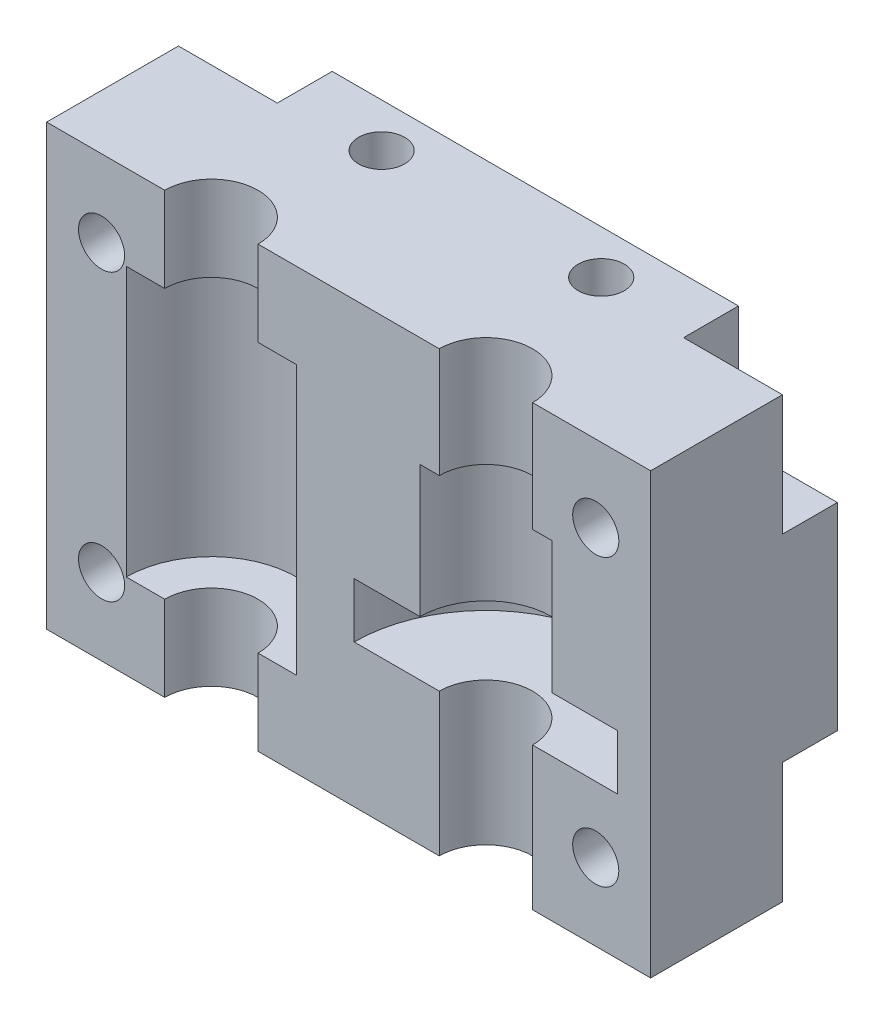
SolidWorks part; units mm, degrees
ref_plane "Plan de face" through (0, 0, 0) normal (0, 0, 1) x (1, 0, 0)
ref_plane "Plan de dessus" through (0, 0, 0) normal (0, 1, 0) x (1, 0, 0)
ref_plane "Plan de droite" through (0, 0, 0) normal (1, 0, 0) x (0, 0, -1)
sketch "Esquisse1" plane through (0, 0, 0) normal (0, 0, 1) x (1, 0, 0)
  line L1 (-27.5, -22.5) -> (27.5, -22.5)
  line L2 (-27.5, -22.5) -> (-27.5, 22.5)
  line L3 (-27.5, 22.5) -> (27.5, 22.5)
  line L4 (27.5, -22.5) -> (27.5, 22.5)
  line L5 (-27.5, -22.5) -> (27.5, 22.5) construction
  line L6 (-27.5, 22.5) -> (27.5, -22.5) construction
  point P0 (0, 0)
  dimension "D1" = 55
  dimension "D2" = 45
extrude "Boss.-Extru.1" add sketch "Esquisse1" along normal blind 12
sketch "Esquisse2" plane through (0, 22.5, 0) normal (0, 1, 0) x (1, 0, 0)
  line L0 (27.5, -12) -> (-27.5, -12) construction
  line L1 (-27.5, -12) -> (-27.5, 0) construction
  line L2 (27.5, -12) -> (27.5, 0) construction
  circle A0 centre (-12.5, -12) radius 4.25
  circle A1 centre (12.5, -12) radius 4.25
  dimension "D1" = 8.5
  dimension "D3" = 8.5
  dimension "D2" = 15
  dimension "D4" = 15
extrude "Enlèv. mat.-Extru.1" cut sketch "Esquisse2" against normal through all
sketch "Esquisse3" plane through (0, 0, 0) normal (0, 1, 0) x (1, 0, 0)
  circle A0 centre (-12.5, -12) radius 7.75
  dimension "D1" = 15.5
extrude "Enlèv. mat.-Extru.2" cut sketch "Esquisse3" against normal blind 12.25 and the other way blind 12.25
sketch "Esquisse9" plane through (0, 0, 12) normal (0, 0, 1) x (1, 0, 0)
  line L0 (-8.25, -22.5) -> (8.25, -22.5) construction
  line L1 (-30.9208, -30.2281) -> (30.1419, -30.2281)
  line L2 (-30.9208, -30.2281) -> (-30.9208, -18)
  line L3 (-30.9208, -18) -> (30.1419, -18)
  line L4 (30.1419, -30.2281) -> (30.1419, -18)
  line L5 (8.25, 22.5) -> (-8.25, 22.5) construction
  line L6 (31.3881, 26.1002) -> (-28.039, 26.1002)
  line L7 (31.3881, 26.1002) -> (31.3881, 18)
  line L8 (31.3881, 18) -> (-28.039, 18)
  line L9 (-28.039, 26.1002) -> (-28.039, 18)
  dimension "D1" = 4.5
  dimension "D2" = 4.5
extrude "Enlèv. mat.-Extru.7" cut sketch "Esquisse9" against normal blind 31
sketch "Sketch1" plane through (0, 0, 0) normal (0, 0, -1) x (-1, 0, 0)
  line L4 (-27.5, -18) -> (27.5, -18)
  line L5 (27.5, -18) -> (27.5, 18)
  line L6 (27.5, 18) -> (-27.5, 18)
  line L7 (-27.5, 18) -> (-27.5, -18)
  line L8 (-27.5, -18) -> (27.5, -18)
  line L9 (27.5, -18) -> (27.5, 18)
  line L10 (27.5, 18) -> (-27.5, 18)
  line L11 (-27.5, 18) -> (-27.5, -18)
  dimension "D1" = 0
extrude "Boss-Extrude1" add sketch "Sketch1" along normal blind 5
sketch "Sketch2" plane through (0, 0, 12) normal (0, 0, 1) x (1, 0, 0)
  line L0 (-27.5, 18) -> (-16.75, 18) construction
  line L1 (-27.5, 18) -> (-27.5, -18) construction
  line L2 (0, 18) -> (0, -18) construction
  line L3 (-8.25, 18) -> (8.25, 18) construction
  line L4 (8.25, -18) -> (-8.25, -18) construction
  line L5 (-27.5, 0) -> (27.5, 0) construction
  line L6 (27.5, -18) -> (27.5, 18) construction
  circle A0 centre (-22.5, 13) radius 2.1
  circle A1 centre (22.5, 13) radius 2.1
  circle A2 centre (22.5, -13) radius 2.1
  circle A3 centre (-22.5, -13) radius 2.1
  dimension "D1" = 4.2
  dimension "D2" = 5
  dimension "D3" = 5
extrude "Cut-Extrude1" cut sketch "Sketch2" against normal through all
sketch "Sketch3" plane through (0, 0, -5) normal (0, 0, -1) x (-1, 0, 0)
  circle A0 centre (-22.5, 13) radius 4
  circle A1 centre (22.5, 13) radius 4
  circle A2 centre (22.5, -13) radius 4
  circle A3 centre (-22.5, -13) radius 4
  dimension "D1" = 8
extrude "Cut-Extrude2" cut sketch "Sketch3" against normal blind 10
sketch "Sketch4" plane through (0, 0, -5) normal (0, 0, -1) x (-1, 0, 0)
  line L0 (-18.5, 13) -> (-18.5, 18)
  line L1 (-22.5, 9) -> (-27.5, 9)
  line L2 (-22.5, -9) -> (-27.5, -9)
  line L3 (-18.5, -13) -> (-18.5, -18)
  line L4 (-27.5, 18) -> (-27.5, -18)
  line L5 (-27.5, -18) -> (27.5, -18)
  line L6 (27.5, -18) -> (27.5, 18)
  line L7 (27.5, 18) -> (-27.5, 18)
  line L8 (-27.5, 18) -> (-27.5, 9)
  line L9 (-27.5, -18) -> (-18.5, -18)
  line L10 (27.5, -18) -> (27.5, -9)
  line L11 (27.5, 18) -> (18.5, 18)
  line L12 (18.5, -13) -> (18.5, -18)
  line L13 (22.5, -9) -> (27.5, -9)
  line L14 (22.5, 9) -> (27.5, 9)
  line L15 (18.5, 13) -> (18.5, 18)
  line L16 (-18.5, 18) -> (-27.5, 18)
  line L17 (-27.5, -9) -> (-27.5, -18)
  line L18 (18.5, -18) -> (27.5, -18)
  line L19 (27.5, 9) -> (27.5, 18)
  circle A0 centre (-22.5, 13) radius 4 construction
  circle A1 centre (-22.5, -13) radius 4 construction
  circle A2 centre (22.5, -13) radius 4 construction
  circle A3 centre (22.5, 13) radius 4 construction
  arc A4 (-18.5, 13) -> (-22.5, 9) centre (-22.5, 13) ccw
  arc A5 (-22.5, -9) -> (-18.5, -13) centre (-22.5, -13) ccw
  arc A6 (18.5, -13) -> (22.5, -9) centre (22.5, -13) ccw
  arc A7 (22.5, 9) -> (18.5, 13) centre (22.5, 13) ccw
  dimension "D1" = 0
extrude "Cut-Extrude3" cut sketch "Sketch4" against normal blind 5
sketch "Sketch5" plane through (0, 18, 0) normal (0, 1, 0) x (1, 0, 0)
  line L0 (-27.5, -12) -> (-27.5, 0) construction
  line L1 (27.5, 0) -> (27.5, 5) construction
  line L2 (-18.5, 5) -> (18.5, 5) construction
  circle A0 centre (-10, 1) radius 2.1
  circle A1 centre (10, 1) radius 2.1
  dimension "D1" = 4.2
  dimension "D2" = 4.2
  dimension "D3" = 17.5
  dimension "D4" = 17.5
  dimension "D5" = 4
  dimension "D6" = 4
extrude "Cut-Extrude4" cut sketch "Sketch5" against normal blind 10
sketch "Sketch7" plane through (0, 18, 0) normal (0, 1, 0) x (1, 0, 0)
  line L10 (18.5, 5) -> (-18.5, 5)
  line L11 (-18.5, 5) -> (-18.5, 0)
  line L12 (-18.5, 0) -> (-27.5, 0)
  line L13 (-27.5, 0) -> (-27.5, -12)
  line L14 (-27.5, -12) -> (-16.75, -12)
  line L15 (-8.25, -12) -> (8.25, -12)
  line L16 (16.75, -12) -> (27.5, -12)
  line L17 (27.5, -12) -> (27.5, 0)
  line L18 (27.5, 0) -> (18.5, 0)
  line L19 (18.5, 0) -> (18.5, 5)
  line L20 (18.5, 5) -> (-18.5, 5)
  line L21 (-18.5, 5) -> (-18.5, 0)
  line L22 (-18.5, 0) -> (-27.5, 0)
  line L23 (-27.5, 0) -> (-27.5, -12)
  line L24 (-27.5, -12) -> (-16.75, -12)
  line L25 (-8.25, -12) -> (8.25, -12)
  line L26 (16.75, -12) -> (27.5, -12)
  line L27 (27.5, -12) -> (27.5, 0)
  line L28 (27.5, 0) -> (18.5, 0)
  line L29 (18.5, 0) -> (18.5, 5)
  circle A0 centre (10, 1) radius 2.1 construction
  circle A1 centre (-10, 1) radius 2.1 construction
  arc A2 (-8.25, -12) -> (-16.75, -12) centre (-12.5, -12) ccw
  arc A3 (16.75, -12) -> (8.25, -12) centre (12.5, -12) ccw
  arc A4 (-8.25, -12) -> (-16.75, -12) centre (-12.5, -12) ccw
  arc A5 (16.75, -12) -> (8.25, -12) centre (12.5, -12) ccw
  circle A6 centre (10, 1) radius 2.1
  circle A7 centre (-10, 1) radius 2.1
  dimension "D1" = 0
extrude "Boss-Extrude4" add sketch "Sketch7" along normal blind 2
sketch "Sketch8" plane through (0, -18, 0) normal (0, -1, 0) x (1, 0, 0)
  line L10 (-27.5, 0) -> (-18.5, 0)
  line L11 (-18.5, 0) -> (-18.5, -5)
  line L12 (-18.5, -5) -> (18.5, -5)
  line L13 (18.5, -5) -> (18.5, 0)
  line L14 (18.5, 0) -> (27.5, 0)
  line L15 (27.5, 0) -> (27.5, 12)
  line L16 (27.5, 12) -> (16.75, 12)
  line L17 (8.25, 12) -> (-8.25, 12)
  line L18 (-16.75, 12) -> (-27.5, 12)
  line L19 (-27.5, 12) -> (-27.5, 0)
  line L20 (-27.5, 0) -> (-18.5, 0)
  line L21 (-18.5, 0) -> (-18.5, -5)
  line L22 (-18.5, -5) -> (18.5, -5)
  line L23 (18.5, -5) -> (18.5, 0)
  line L24 (18.5, 0) -> (27.5, 0)
  line L25 (27.5, 0) -> (27.5, 12)
  line L26 (27.5, 12) -> (16.75, 12)
  line L27 (8.25, 12) -> (-8.25, 12)
  line L28 (-16.75, 12) -> (-27.5, 12)
  line L29 (-27.5, 12) -> (-27.5, 0)
  circle A0 centre (-10, -1) radius 2.1 construction
  circle A1 centre (10, -1) radius 2.1 construction
  arc A2 (8.25, 12) -> (16.75, 12) centre (12.5, 12) ccw
  arc A3 (-16.75, 12) -> (-8.25, 12) centre (-12.5, 12) ccw
  arc A4 (8.25, 12) -> (16.75, 12) centre (12.5, 12) ccw
  arc A5 (-16.75, 12) -> (-8.25, 12) centre (-12.5, 12) ccw
  circle A6 centre (10, -1) radius 2.1
  circle A7 centre (-10, -1) radius 2.1
  dimension "D1" = 0
extrude "Boss-Extrude5" add sketch "Sketch8" along normal blind 2
ref_plane "Plan1" through (0, -2, 0) normal (0, -1, 0) x (-1, 0, 0)
sketch "Sketch9" plane through (0, 0, -5) normal (0, 0, -1) x (-1, 0, 0)
  line L0 (-27.5, 20) -> (-27.5, 9) construction
  line L1 (-13.5, 16) -> (-6.5, 16)
  line L2 (-13.5, 16) -> (-13.5, 12.8)
  line L3 (-13.5, 12.8) -> (-6.5, 12.8)
  line L4 (-6.5, 16) -> (-6.5, 12.8)
  line L5 (-18.5, 20) -> (18.5, 20) construction
  line L6 (0, 20) -> (0, -9.1772) construction
  line L7 (13.5, 12.8) -> (6.5, 12.8)
  line L8 (6.5, 16) -> (6.5, 12.8)
  line L9 (13.5, 16) -> (6.5, 16)
  line L10 (13.5, 16) -> (13.5, 12.8)
  line L11 (-27.5, 0) -> (-8.3783, 0) construction
  line L12 (-27.5, 9) -> (-27.5, -9) construction
  line L13 (13.5, -16) -> (13.5, -12.8)
  line L14 (13.5, -16) -> (6.5, -16)
  line L15 (6.5, -16) -> (6.5, -12.8)
  line L16 (13.5, -12.8) -> (6.5, -12.8)
  line L17 (-13.5, -12.8) -> (-6.5, -12.8)
  line L18 (-6.5, -16) -> (-6.5, -12.8)
  line L19 (-13.5, -16) -> (-6.5, -16)
  line L20 (-13.5, -16) -> (-13.5, -12.8)
  point P4 (-10, 16)
  dimension "D1" = 7
  dimension "D2" = 17.5
  dimension "D3" = 4
  dimension "D4" = 3.2
extrude "Cut-Extrude6" cut sketch "Sketch9" against normal blind 8
ref_plane "Plane1" through (0, 0, 0) normal (-1, 0, 0) x (0, 0, 1)
mirror "Mirror1" [suppressed] about plane through (0, 0, 0) normal (-1, 0, 0)
sketch "Esquisse10" [suppressed] plane through (0, 0, -5) normal (0, 0, -1) x (-1, 0, 0)
  line L0 (27.5, -20) -> (-27.5, 20) construction
  line L2 (15, 5) -> (-15, 5)
  line L3 (15, 5) -> (15, -5)
  line L4 (15, -5) -> (-15, -5)
  line L5 (-15, 5) -> (-15, -5)
  line L6 (15, 5) -> (-15, -5) construction
  line L7 (15, -5) -> (-15, 5) construction
  point P4 (0, 0)
  dimension "D1" = 10
  dimension "D2" = 30
extrude "Boss.-Extru.2" [suppressed] add sketch "Esquisse10" along normal blind 80
fillet "Congé1" [suppressed] radius 10
sketch "Esquisse11" [suppressed] plane through (0, -5, 0) normal (0, -1, 0) x (1, 0, 0)
  line L0 (0, -5) -> (0, -85) construction
  line L1 (-18.5, -5) -> (18.5, -5) construction
  line L2 (5, -85) -> (-5, -85) construction
  circle A0 centre (0, -70) radius 4
  dimension "D1" = 8
  dimension "D2" = 15
extrude "Enlèv. mat.-Extru.8" [suppressed] cut sketch "Esquisse11" against normal through all
sketch "Esquisse12" plane through (0, -2, 0) normal (0, 1, 0) x (1, 0, 0)
  circle A0 centre (12.5, -12) radius 6
  dimension "D1" = 12
extrude "Enlèv. mat.-Extru.9" cut sketch "Esquisse12" along normal blind 12
sketch "Esquisse13" plane through (0, -2, 0) normal (0, 1, 0) x (1, 0, 0)
  circle A0 centre (12.5, -12) radius 12
  dimension "D1" = 24
extrude "Enlèv. mat.-Extru.10" cut sketch "Esquisse13" against normal blind 5
move or copy body "Body-Move/Copy1" [suppressed] bodies to move or copy 135
